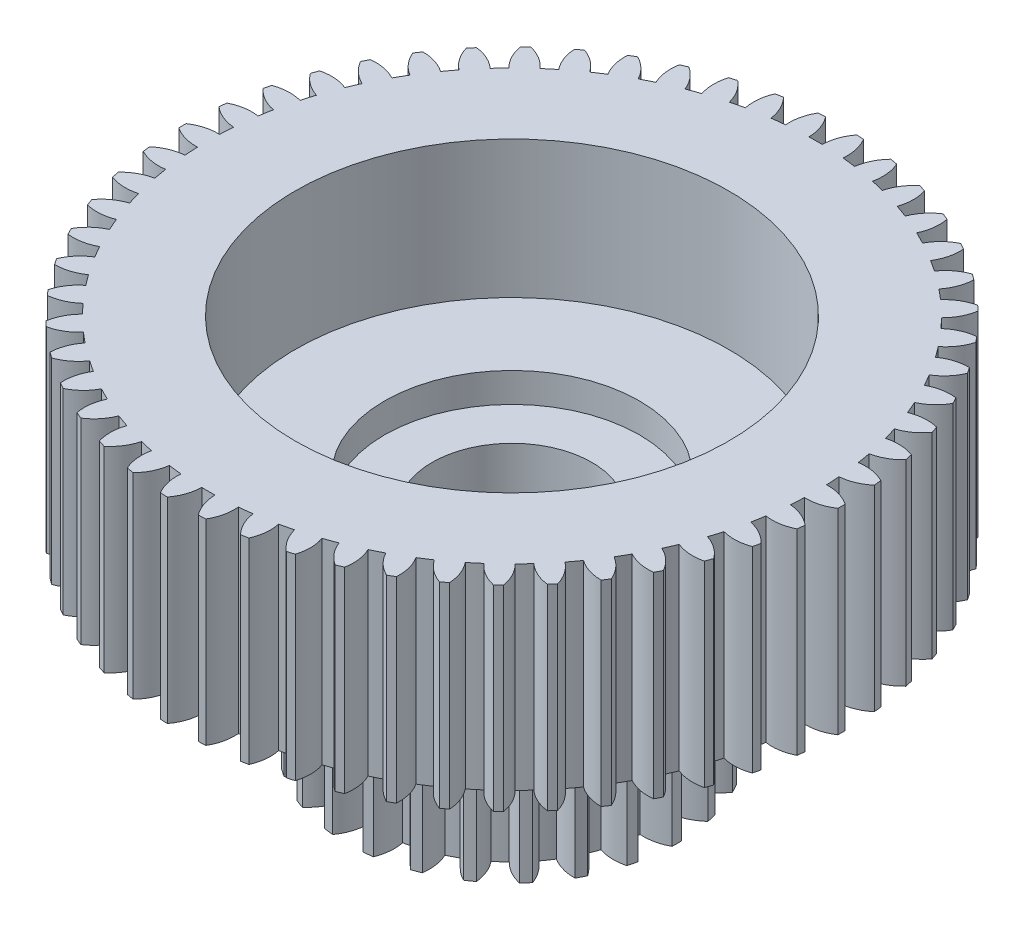
SolidWorks part; units mm, degrees
ref_plane "Ebene vorne" through (0, 0, 0) normal (0, 0, 1) x (1, 0, 0)
ref_plane "Ebene oben" through (0, 0, 0) normal (0, 1, 0) x (1, 0, 0)
ref_plane "Ebene rechts" through (0, 0, 0) normal (1, 0, 0) x (0, 0, -1)
sketch "Skizze1" plane through (0, 0, 0) normal (0, 1, 0) x (1, 0, 0)
  circle A0 centre (0, 0) radius 8.4
  circle A1 centre (0, 0) radius 4.075
  dimension "D2" = 8.15
  dimension "D1" = 16.8
extrude "Aufsatz-Linear austragen1" add sketch "Skizze1" along normal blind 9.1
sketch "Skizze2" plane through (0, 9.1, 0) normal (0, 1, 0) x (1, 0, 0)
  circle A0 centre (0, 0) radius 16.8
  circle A1 centre (0, 0) radius 4.075
  dimension "D1" = 33.6
  dimension "D2" = 8.15
extrude "Aufsatz-Linear austragen2" add sketch "Skizze2" along normal blind 10
sketch "Skizze3" plane through (0, 19.1, 0) normal (0, 1, 0) x (1, 0, 0)
  circle A0 centre (0, 0) radius 11.05
  dimension "D1" = 22.1
extrude "Schnitt-Linear austragen1" cut sketch "Skizze3" against normal blind 7
sketch "Skizze5" plane through (0, 19.1, 0) normal (0, 1, 0) x (1, 0, 0)
  line L0 (0, 0) -> (0, 16.8) construction
  line L1 (0, 0) -> (-0.3367, 15.4763) construction
  line L2 (0, 0) -> (0.9768, 16.7716) construction
  line L3 (-0.4712, 16.1931) -> (0.4712, 16.1931) construction
  line L4 (0.4712, 16.1931) -> (1.4119, 16.1384) construction
  line L5 (0, 14.8986) -> (-0.6869, 16.786) construction
  circle A0 centre (0, 0) radius 16.8
  circle A1 centre (0, 0) radius 16.2 construction
  circle A2 centre (0, 0) radius 15.48
  arc A3 (-0.792, 16.7813) -> (-0.3367, 15.4763) centre (-2.5744, 15.4277) cw
  arc A4 (0.792, 16.7813) -> (0.3367, 15.4763) centre (2.5744, 15.4277) ccw
  dimension "D1" = 33.6
  dimension "D2" = 32.4
  dimension "D3" = 30.96
  dimension "D4" = 3.333
  dimension "D5" = 20
extrude "Schnitt-Linear austragen2" cut sketch "Skizze5" against normal up to surface (10 mm away) contours A4 A0 A3 A2 region at (0, 19.1, -16.2378) up to face at (0, 9.1, 8.4)
pattern_circular "Kreismuster1" count 54 over 360 about axis through (0, 12.1, 0) along (0, 1, 0) of "Schnitt-Linear austragen2"
sketch "Skizze6" plane through (0, 0, 0) normal (0, -1, 0) x (1, 0, 0)
  line L0 (0, 0) -> (0, 8.4) construction
  line L1 (0, 0) -> (-0.328, 7.0724) construction
  line L2 (0, 0) -> (1.0125, 8.3388) construction
  line L3 (-0.471, 7.7858) -> (0.471, 7.7858) construction
  line L4 (0.471, 7.7858) -> (1.406, 7.6722) construction
  line L5 (0, 6.4918) -> (-0.6844, 8.3721) construction
  circle A0 centre (0, 0) radius 8.4
  circle A1 centre (0, 0) radius 7.8 construction
  circle A2 centre (0, 0) radius 7.08
  arc A3 (-0.7757, 8.3641) -> (-0.328, 7.0724) centre (-2.7381, 6.9606) cw
  arc A4 (0.7757, 8.3641) -> (0.328, 7.0724) centre (2.7381, 6.9606) ccw
  dimension "D1" = 16.8
  dimension "D5" = 20
  dimension "D2" = 15.6
  dimension "D3" = 14.16
  dimension "D4" = 6.923
extrude "Schnitt-Linear austragen3" cut sketch "Skizze6" against normal up to surface (9.1 mm away) contours A4 A0 A3 A2 region at (0, 0, 7.8346) up to face at (0, 9.1, 8.4)
pattern_circular "Kreismuster2" count 26 over 360 about axis through (0, 9.1, 0) along (0, -1, 0) of "Schnitt-Linear austragen3" reverse direction yes
sketch "Skizze7" plane through (0, 12.1, 0) normal (0, 1, 0) x (1, 0, 0)
  circle A0 centre (0, 0) radius 6.5
  dimension "D1" = 13
extrude "Schnitt-Linear austragen4" cut sketch "Skizze7" against normal blind 1.5
equation "\"Tooth1\"= 54"
equation "\"Tooth2\"= 26"
equation "\"Module\"= 0.6mm"
equation "\"D1@Skizze2\"=(\"Tooth1\"+2)*\"Module\""
equation "\"D1@Skizze1\"=(\"Tooth2\"+2)*\"Module\""
equation "\"D1@Skizze5\"=(\"Tooth1\"+2)*\"Module\""
equation "\"D2@Skizze5\"=\"Tooth1\"*\"Module\""
equation "\"D3@Skizze5\"=(\"Module\"*\"Tooth1\"- (\"Module\"*if(\"Module\" => 1.25,2.25,2.4)))"
equation "\"D4@Skizze5\"=180/\"Tooth1\""
equation "\"D1@Kreismuster1\"=\"Tooth1\""
equation "\"D3@Skizze6\"=(\"Module\"*\"Tooth2\"- (\"Module\"*if(\"Module\" => 1.25,2.25,2.4)))"
equation "\"D2@Skizze6\"=\"Tooth2\"*\"Module\""
equation "\"D1@Skizze6\"=(\"Tooth2\"+2)*\"Module\""
equation "\"D4@Skizze6\"=180/\"Tooth2\""
equation "\"D1@Kreismuster2\"=\"Tooth2\""
